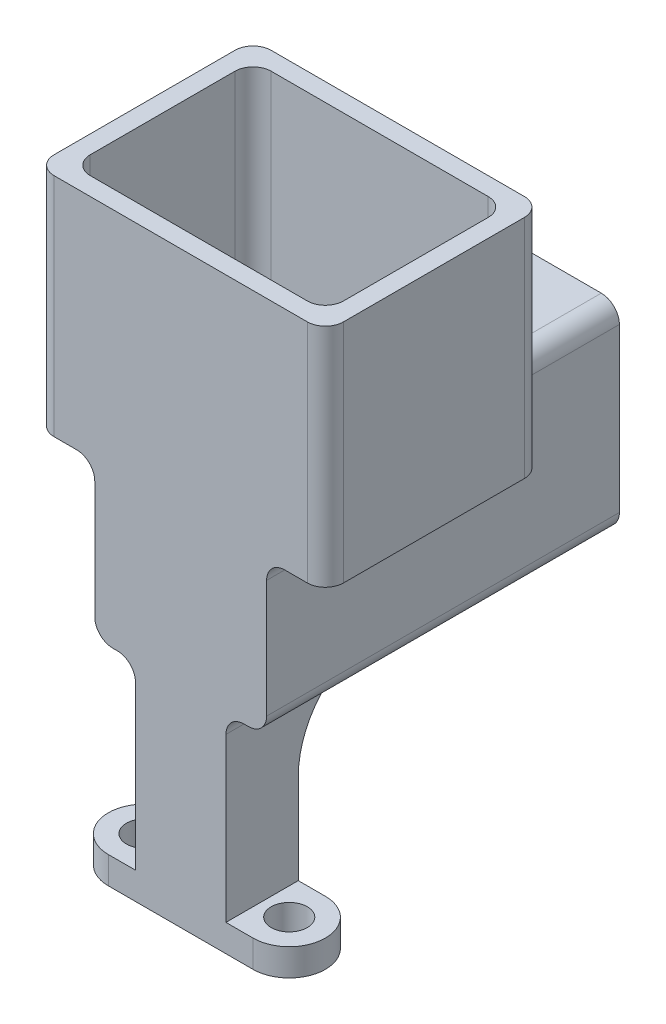
SolidWorks part; units mm, degrees
ref_plane "前视基准面" through (0, 0, 0) normal (0, 0, 1) x (1, 0, 0)
ref_plane "上视基准面" through (0, 0, 0) normal (0, 1, 0) x (1, 0, 0)
ref_plane "右视基准面" through (0, 0, 0) normal (1, 0, 0) x (0, 0, -1)
other "Configuration Table"
sketch "草图1" plane through (0, 0, 0) normal (0, 1, 0) x (1, 0, 0)
  line L0 (-8, 0) -> (8, 0) construction
  line L1 (-8, 4) -> (8, 4)
  line L2 (-8, -4) -> (8, -4)
  arc A0 (-8, 4) -> (-8, -4) centre (-8, 0) ccw
  arc A1 (8, -4) -> (8, 4) centre (8, 0) ccw
  circle A2 centre (8, 0) radius 2
  circle A3 centre (-8, 0) radius 2
  point P2 (0, 0)
  dimension "D2" = 4
  dimension "D3" = 4
  dimension "D1" = 16
  dimension "D4" = 8
extrude "凸台-拉伸1" add sketch "草图1" along normal blind 3
sketch "草图2" plane through (0, 3, 0) normal (0, 1, 0) x (1, 0, 0)
  line L0 (8, 4) -> (-8, 4) construction
  line L1 (-5, -4) -> (5, -4)
  line L2 (-5, -4) -> (-5, 4)
  line L3 (-5, 4) -> (5, 4)
  line L4 (5, -4) -> (5, 4)
  line L5 (-5, -4) -> (5, 4) construction
  line L6 (-5, 4) -> (5, -4) construction
  point P0 (0, 0)
  dimension "D1" = 10
extrude "凸台-拉伸2" add sketch "草图2" along normal blind 20
sketch "草图3" plane through (0, 23, 0) normal (0, 1, 0) x (1, 0, 0)
  line L0 (0, -4) -> (0, 4) construction
  line L5 (-5, -4) -> (5, -4) construction
  line L6 (-9.5, -4) -> (9.5, -4)
  line L8 (-9.5, 35) -> (9.5, 35)
  line L9 (9.5, -4) -> (9.5, 35)
  line L10 (-9.5, -4) -> (-9.5, 35)
  point P10 (0, -4)
  point P11 (0, 35)
  dimension "D1" = 9.5
  dimension "D2" = 39
extrude "凸台-拉伸3" add sketch "草图3" along normal blind 22
sketch "草图4" plane through (0, 0, -35) normal (0, 0, -1) x (-1, 0, 0)
  line L0 (-5, 23) -> (5, 23) construction
  line L1 (-7.5, 43) -> (7.5, 43)
  line L2 (-7.5, 43) -> (-7.5, 25)
  line L3 (-7.5, 25) -> (7.5, 25)
  line L4 (7.5, 43) -> (7.5, 25)
  line L5 (9.5, 45) -> (9.5, 23) construction
  line L6 (-9.5, 45) -> (-9.5, 23) construction
  line L7 (-9.5, 45) -> (9.5, 45) construction
  dimension "D1" = 2
  dimension "D2" = 2
  dimension "D3" = 2
  dimension "D4" = 2
extrude "切除-拉伸1" cut sketch "草图4" against normal blind 31
sketch "草图5" plane through (0, 45, 0) normal (0, 1, 0) x (1, 0, 0)
  line L0 (9.5, -4) -> (9.5, 35) construction
  line L1 (-7.5, 4) -> (7.5, 4)
  line L2 (-7.5, 4) -> (-7.5, 12)
  line L3 (-7.5, 12) -> (7.5, 12)
  line L4 (7.5, 4) -> (7.5, 12)
  line L5 (-7.5, 4) -> (7.5, 12) construction
  line L6 (-7.5, 12) -> (7.5, 4) construction
  line L7 (-9.5, 35) -> (-9.5, -4) construction
  line L8 (-9.5, -4) -> (9.5, -4) construction
  point P0 (0, 8)
  dimension "D1" = 2
  dimension "D2" = 2
  dimension "D3" = 8
  dimension "D4" = 8
extrude "切除-拉伸2" cut sketch "草图5" against normal blind 5 contours L2 L1 L4 L3
sketch "草图6" plane through (0, 45, 0) normal (0, 1, 0) x (1, 0, 0)
  line L0 (-7.5, 12) -> (7.5, 4) construction
  line L1 (7.5, 12) -> (-7.5, 4) construction
  line L3 (-16, 20) -> (16, 20)
  line L4 (-16, 20) -> (-16, -4)
  line L5 (-16, -4) -> (16, -4)
  line L6 (16, 20) -> (16, -4)
  line L7 (-16, 20) -> (16, -4) construction
  line L8 (-16, -4) -> (16, 20) construction
  point P8 (0, 8)
  dimension "D1" = 24
  dimension "D2" = 32
extrude "凸台-拉伸5" add sketch "草图6" along normal blind 20
sketch "草图7" plane through (0, 65, 0) normal (0, 1, 0) x (1, 0, 0)
  line L0 (-16, 20) -> (16, -4) construction
  line L1 (16, 20) -> (-16, -4) construction
  line L2 (-16, -4) -> (16, -4) construction
  line L3 (9.5, 20) -> (-9.5, 20) construction
  line L4 (-14, -2) -> (14, -2)
  line L5 (-14, -2) -> (-14, 18)
  line L6 (-14, 18) -> (14, 18)
  line L7 (14, -2) -> (14, 18)
  line L8 (-14, -2) -> (14, 18) construction
  line L9 (-14, 18) -> (14, -2) construction
  line L10 (16, -4) -> (16, 20) construction
  point P9 (0, 8)
  dimension "D1" = 2
  dimension "D2" = 2
extrude "切除-拉伸3" cut sketch "草图7" against normal blind 20
sketch "草图8" plane through (0, 45, 0) normal (0, 1, 0) x (1, 0, 0)
  line L9 (16, -4) -> (9.5, -4)
  line L10 (16, -4) -> (16, 20)
  line L11 (16, 20) -> (9.5, 20)
  line L12 (9.5, -4) -> (9.5, 20)
  line L13 (-16, -4) -> (-9.5, -4)
  line L14 (-16, -4) -> (-16, 20)
  line L15 (-16, 20) -> (-9.5, 20)
  line L16 (-9.5, -4) -> (-9.5, 20)
  line M16 (-9.5, 18) -> (-9.5, -2)
extrude "凸台-拉伸6" add sketch "草图8" against normal blind 5 contours L13 L16 L15 L14 M16 | L10 L9 L12 L11 region at (-12.75, 45, -8)
sketch "草图9" plane through (0, 25, 0) normal (0, 1, 0) x (1, 0, 0)
  line L0 (-7.5, 4) -> (7.5, 4)
  line L1 (-7.5, 4) -> (-7.5, 14)
  line L2 (7.5, 4) -> (7.5, 14)
  line L3 (-7.5, 14) -> (7.5, 14)
  dimension "D1" = 10
extrude "凸台-拉伸7" add sketch "草图9" along normal blind 2
fillet "圆角1" radius 2 1 edges at (16, 52.5, -20)
fillet "圆角2" radius 2 1 edges at (-16, 52.5, -20)
fillet "圆角3" radius 2 1 edges at (-16, 52.5, 4)
fillet "圆角4" radius 2 1 edges at (16, 52.5, 4)
fillet "圆角5" radius 2 1 edges at (14, 55, 2)
fillet "圆角6" radius 2 1 edges at (-14, 55, 2)
fillet "圆角7" radius 2 1 edges at (-14, 55, -18)
fillet "圆角8" radius 2 1 edges at (14, 55, -18)
fillet "圆角9" radius 2 1 edges at (-7.5, 36, -4)
fillet "圆角10" radius 2 1 edges at (7.5, 36, -4)
fillet "圆角11" radius 2 1 edges at (7.5, 44, -12)
fillet "圆角12" radius 2 1 edges at (-7.5, 44, -12)
fillet "圆角13" radius 2 1 edges at (-9.5, 45, -27.5)
fillet "圆角14" radius 2 1 edges at (9.5, 45, -27.5)
fillet "圆角15" radius 2 1 edges at (9.5, 23, -15.5)
fillet "圆角16" radius 2 1 edges at (-9.5, 23, -15.5)
fillet "圆角17" radius 2 1 edges at (9.5, 40, -8)
fillet "圆角18" radius 2 1 edges at (-9.5, 40, -8)
fillet "圆角19" radius 2 1 edges at (5, 23, 0)
fillet "圆角20" radius 2 1 edges at (-5, 23, 0)
fillet "圆角21" radius 10 1 edges at (0, 23, -4)
